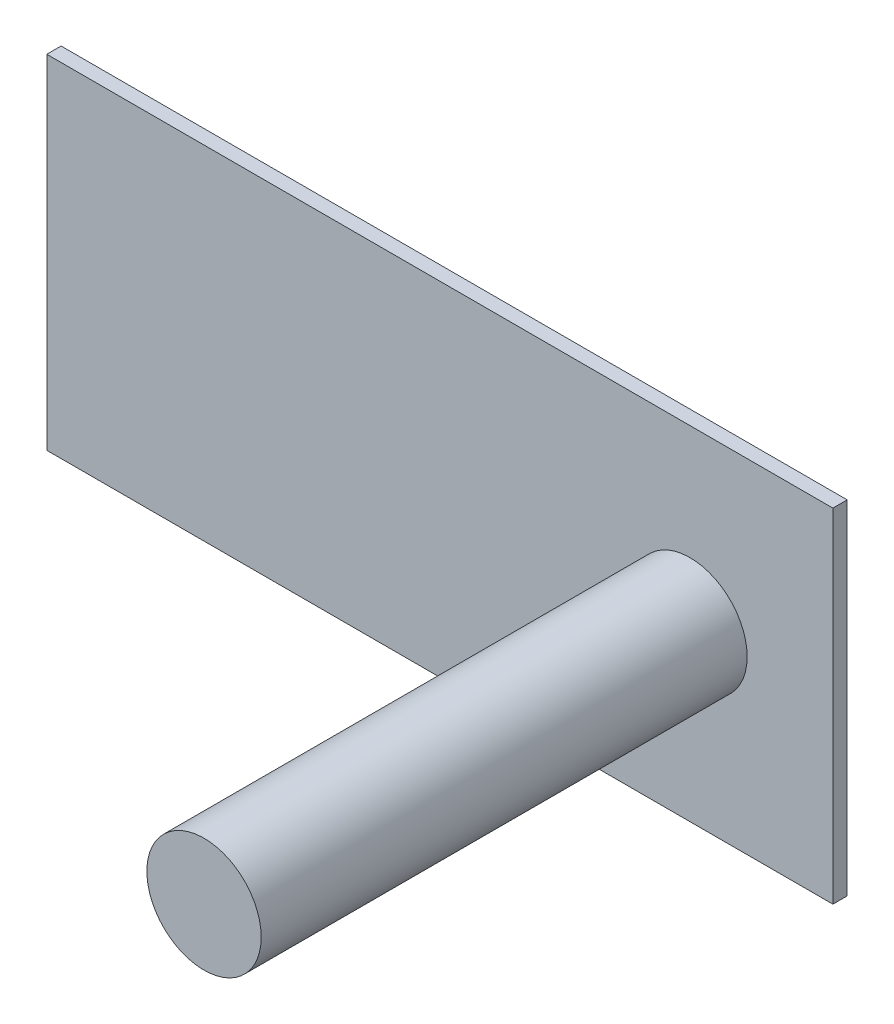
SolidWorks part; units mm, degrees
ref_plane "Front Plane" through (0, 0, 0) normal (0, 0, 1) x (1, 0, 0)
ref_plane "Top Plane" through (0, 0, 0) normal (0, 1, 0) x (1, 0, 0)
ref_plane "Right Plane" through (0, 0, 0) normal (1, 0, 0) x (0, 0, -1)
sketch "Sketch2" plane through (0, 0, 0) normal (0, 0, 1) x (1, 0, 0)
  line L4 (63.5, 38.1) -> (-63.5, 38.1)
  line L5 (63.5, -38.1) -> (63.5, 38.1)
  line L6 (-63.5, -38.1) -> (63.5, -38.1)
  line L7 (-63.5, 38.1) -> (-63.5, -38.1)
  line L8 (63.5, 38.1) -> (-63.5, 38.1)
  line L9 (63.5, -38.1) -> (63.5, 38.1)
  line L10 (-63.5, -38.1) -> (63.5, -38.1)
  line L11 (-63.5, 38.1) -> (-63.5, -38.1)
  circle A1 centre (25.4, 0) radius 12.7
  circle A2 centre (25.4, 0) radius 12.7
  dimension "D1" = 0
  dimension "D2" = 0
sketch "Sketch3" plane through (0, 0, 0) normal (0, 1, 0) x (1, 0, 0)
  line L4 (-63.5, 12.7) -> (-63.5, -25.4)
  line L5 (-63.5, -25.4) -> (63.5, -25.4)
  line L6 (63.5, -25.4) -> (63.5, 0)
  line L7 (-18.5941, 12.7) -> (-63.5, 12.7)
  line L8 (-63.5, 12.7) -> (-63.5, -25.4)
  line L9 (-63.5, -25.4) -> (63.5, -25.4)
  line L10 (63.5, -25.4) -> (63.5, 0)
  line L11 (-18.5941, 12.7) -> (-63.5, 12.7)
  arc A3 (63.5, 0) -> (25.4, 38.1) centre (25.4, 0) ccw
  arc A4 (25.4, 38.1) -> (-7.5956, 19.05) centre (25.4, 0) ccw
  arc A5 (-18.5941, 12.7) -> (-7.5956, 19.05) centre (-18.5941, 25.4) ccw
  arc A6 (63.5, 0) -> (25.4, 38.1) centre (25.4, 0) ccw
  arc A7 (25.4, 38.1) -> (-7.5956, 19.05) centre (25.4, 0) ccw
  arc A8 (-18.5941, 12.7) -> (-7.5956, 19.05) centre (-18.5941, 25.4) ccw
  dimension "D1" = 0
sketch "Sketch6" plane through (0, 0, 0) normal (0, 1, 0) x (1, 0, 0)
  line L0 (25.4, 50.8) -> (25.4, -38.1) construction
  line L1 (25.4, 50.8) -> (25.4, -38.1)
sketch "Sketch4" plane through (0, 0, 0) normal (0, 0, 1) x (1, 0, 0)
  circle A0 centre (25.4, 0) radius 12.7 construction
  circle A1 centre (25.4, 0) radius 12.7 construction
  circle A2 centre (25.4, 0) radius 10.16
  dimension "D1" = 2.54
extrude "Boss-Extrude1" add sketch "Sketch4" along normal up to vertex (38.1 mm away) and the other way up to vertex (50.8 mm away) up to point (25.4, 0, 38.1) other way up to point (25.4, 0, -50.8)
sketch "Sketch7" plane through (0, 0, -50.8) normal (0, 0, -1) x (-1, 0, 0)
  line L0 (88.9, 30.48) -> (88.9, -30.48) construction
  line L1 (-50.8, -30.48) -> (88.9, -30.48)
  line L2 (-50.8, -30.48) -> (-50.8, 30.48)
  line L3 (-50.8, 30.48) -> (88.9, 30.48)
  line L4 (88.9, -30.48) -> (88.9, 30.48)
  line L5 (88.9, -30.48) -> (63.5, -30.48) construction
  dimension "D1" = 25.4
extrude "Boss-Extrude2" add sketch "Sketch7" against normal blind 2.54
